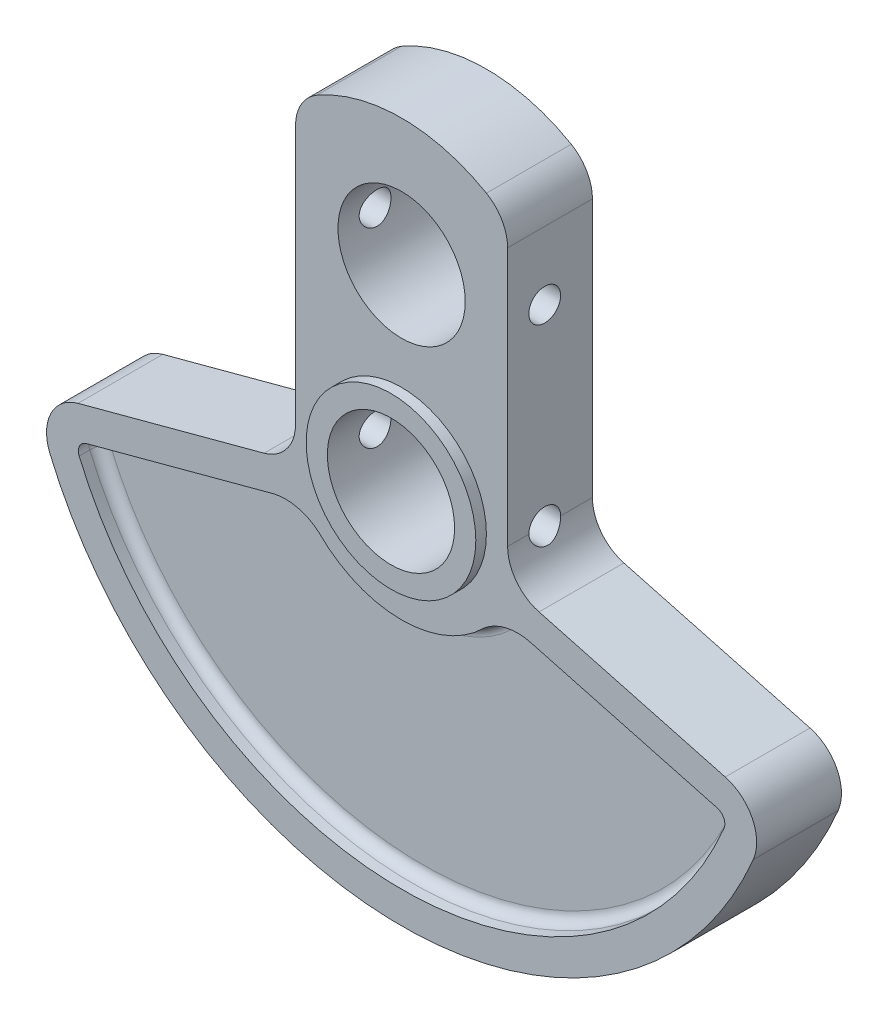
SolidWorks part; units mm, degrees
ref_plane "Front Plane" through (0, 0, 0) normal (0, 0, 1) x (1, 0, 0)
ref_plane "Top Plane" through (0, 0, 0) normal (0, 1, 0) x (1, 0, 0)
ref_plane "Right Plane" through (0, 0, 0) normal (1, 0, 0) x (0, 0, -1)
sketch "Sketch1" plane through (0, 0, 0) normal (0, 0, 1) x (1, 0, 0)
  line L0 (0, 39.7535) -> (0, -39.7535) construction
  line L1 (-9.704, 0) -> (9.704, 0) construction
  line L2 (0, 0) -> (0, 18) construction
  line L3 (10, 24.3923) -> (10, 0)
  line L4 (12.9647, -3.8637) -> (30.5217, -8.5681)
  line L5 (-12.9647, -3.8637) -> (-30.5217, -8.5681)
  line L6 (-10, 24.3923) -> (-10, 0)
  line L7 (-12.1883, -6.7615) -> (-29.7453, -11.4659)
  line L10 (12.1883, -6.7615) -> (29.7453, -11.4659)
  line L11 (7, 24.3923) -> (7, 0) construction
  line L12 (-7, 24.3923) -> (-7, 0) construction
  circle A0 centre (0, 0) radius 6
  circle A1 centre (0, 0) radius 8
  circle A2 centre (0, 18) radius 6
  circle A3 centre (0, 18) radius 8
  arc A4 (10, 0) -> (12.9647, -3.8637) centre (14, 0) ccw
  arc A5 (33.1723, -13.9858) -> (-33.1723, -13.9858) centre (0, 0) cw
  arc A6 (30.5217, -8.5681) -> (33.1723, -13.9858) centre (29.4864, -12.4318) cw
  arc A8 (-30.5217, -8.5681) -> (-33.1723, -13.9858) centre (-29.4864, -12.4318) ccw
  arc A9 (-10, 0) -> (-12.9647, -3.8637) centre (-14, 0) cw
  arc A10 (-10, 24.3923) -> (-8, 27.8564) centre (-6, 24.3923) cw
  arc A11 (10, 24.3923) -> (8, 27.8564) centre (6, 24.3923) ccw
  arc A12 (-8, 27.8564) -> (8, 27.8564) centre (0, 14) cw
  arc A13 (30.4079, -12.8203) -> (-30.4079, -12.8203) centre (0, 0) cw
  arc A14 (-29.7453, -11.4659) -> (-30.4079, -12.8203) centre (-29.4864, -12.4318) ccw
  arc A20 (29.7453, -11.4659) -> (30.4079, -12.8203) centre (29.4864, -12.4318) cw
  arc A21 (-6.5, 25.2583) -> (6.5, 25.2583) centre (0, 14) cw construction
  arc A22 (7, 24.3923) -> (6.5, 25.2583) centre (6, 24.3923) ccw construction
  arc A23 (-7, 24.3923) -> (-6.5, 25.2583) centre (-6, 24.3923) cw construction
  arc A24 (-7, 0) -> (-12.1883, -6.7615) centre (-14, 0) cw construction
  arc A25 (7, 0) -> (12.1883, -6.7615) centre (14, 0) ccw construction
  arc A26 (-7.8081, -7.7481) -> (7.8081, -7.7481) centre (0, 0) ccw
  arc A27 (-12.1883, -6.7615) -> (-7.8081, -7.7481) centre (-10.9381, -11.4273) cw
  circle A28 centre (0, 0) radius 11 construction
  arc A29 (12.1883, -6.7615) -> (7.8081, -7.7481) centre (10.9381, -11.4273) ccw
  point P4 (0, 0)
  point P8 (0, 0)
  point P38 (0, 30)
  dimension "D1" = 16
  dimension "D2" = 12
  dimension "D5" = 4
  dimension "D6" = 4
  dimension "D7" = 36
  dimension "D8" = 30
  dimension "D9" = 16
  dimension "D10" = 4
  dimension "D4" = 18
  dimension "D11" = 20
  dimension "D12" = 150
  dimension "D13" = 3
  dimension "D14" = 3
  dimension "D3" = 2
extrude "Boss-Extrude2" add sketch "Sketch1" against normal blind 5 contours A3 A2 region at (-7.7737, 18, 0)
extrude "Boss-Extrude3" add sketch "Sketch1<4>" along normal blind 4 contours A3 A2 region at (-7.7737, 18, 0)
sketch "Sketch1<4>" plane through (0, 0, 0) normal (0, 0, 1) x (1, 0, 0) same geometry as "Sketch1"
extrude "Boss-Extrude4" add sketch "Sketch1<8>" against normal blind 4 separate body contours A1 A0 region at (-7.7737, 0, 0)
sketch "Sketch1<8>" plane through (0, 0, 0) normal (0, 0, 1) x (1, 0, 0) same geometry as "Sketch1"
extrude "Boss-Extrude5" add sketch "Sketch1<9>" along normal blind 5 contours A1 A0 region at (-7.7737, 0, 0)
sketch "Sketch1<9>" plane through (0, 0, 0) normal (0, 0, 1) x (1, 0, 0) same geometry as "Sketch1"
extrude "Boss-Extrude6" add sketch "Sketch1<10>" along normal mid plane 8 contours A12 A10 L6 A9 L5 A8 A5 A6 L4 A4 L3 A11 A29 L10 A20 A13 A14 L7 A27 A26 A3 A1 region at (9.0597, 12.1962, 0)
sketch "Sketch1<10>" plane through (0, 0, 0) normal (0, 0, 1) x (1, 0, 0) same geometry as "Sketch1"
extrude "Boss-Extrude7" add sketch "Sketch1<11>" along normal mid plane 4 contours L10 A29 A26 A27 L7 A14 A13 A20 region at (0, -18.9969, 0)
sketch "Sketch1<11>" plane through (0, 0, 0) normal (0, 0, 1) x (1, 0, 0) same geometry as "Sketch1"
sketch "Sketch2" plane through (0, 0, 0) normal (1, 0, 0) x (0, 0, -1)
  line L0 (-5, -6) -> (4, 6) construction
  line L1 (0, 0) -> (0, -39.5171) construction
  line L2 (4, -12.8203) -> (4, -33) construction
  line L3 (4, -9.2679) -> (4, -11) construction
  line L4 (4, -6) -> (4, 6) construction
  line L5 (-5, 6) -> (-5, -6) construction
  line L6 (2.5, -32.134) -> (4, -33) construction
  line L7 (4, -6) -> (4, 6) construction
  line L8 (2, -11) -> (2, -31.2679) construction
  line L9 (-5, 6) -> (-5, -6) construction
  line L11 (-4, 24) -> (-4, 12) construction
  line L12 (4, -9.2679) -> (2.5, -10.134) construction
  line L13 (-4, -12.8203) -> (-4, -11) construction
  line L17 (4, -12.8203) -> (4, -11) construction
  line L18 (-4, 24) -> (-4, 12) construction
  line L19 (-4, -9.2679) -> (-2.5, -10.134) construction
  line L20 (-4, -7.7481) -> (-4, -11) construction
  line L21 (-2, -11) -> (-2, -31.2679) construction
  line L22 (-2.5, -32.134) -> (-4, -33) construction
  line L23 (-4, -12.8203) -> (-4, -33) construction
  line L25 (-4, -9.2679) -> (-4, -11) construction
  line L26 (-4, -12.8203) -> (-4, -33) construction
  circle A0 centre (-0.5, 18) radius 1.5
  circle A1 centre (-0.5, 0) radius 1.5
  arc A2 (-2.5, -10.134) -> (-2, -11) centre (-3, -11) cw construction
  arc A3 (-2, -31.2679) -> (-2.5, -32.134) centre (-3, -31.2679) cw construction
  arc A4 (2, -31.2679) -> (2.5, -32.134) centre (3, -31.2679) ccw construction
  arc A5 (2.5, -10.134) -> (2, -11) centre (3, -11) ccw construction
  point P4 (4, 0)
  point P18 (-4, 18)
  dimension "D1" = 3
  dimension "D3" = 3
  dimension "D2" = 1
  dimension "D4" = 1
  dimension "D5" = 2
  dimension "D6" = 120
  dimension "D7" = 120
extrude "Cut-Extrude1" cut sketch "Sketch2" against normal mid plane 148 contours A0 | A1 | L12 A5 L8 A4 L6 L2 L3 | A3 L21 A2 L19 L25 L26 L22 region at (0, 18, 0.5) region at (0, 0, 0.5)
fillet "Fillet2" radius 1 8 edges at (30.3847, -11.9923, 2) (0, -33, 2) (-30.3847, -11.9923, 2) (-20.9668, -9.1137, 2) (-9.8766, -6.715, 2) (0, -11, 2) (9.8766, -6.715, 2) (20.9668, -9.1137, 2)
